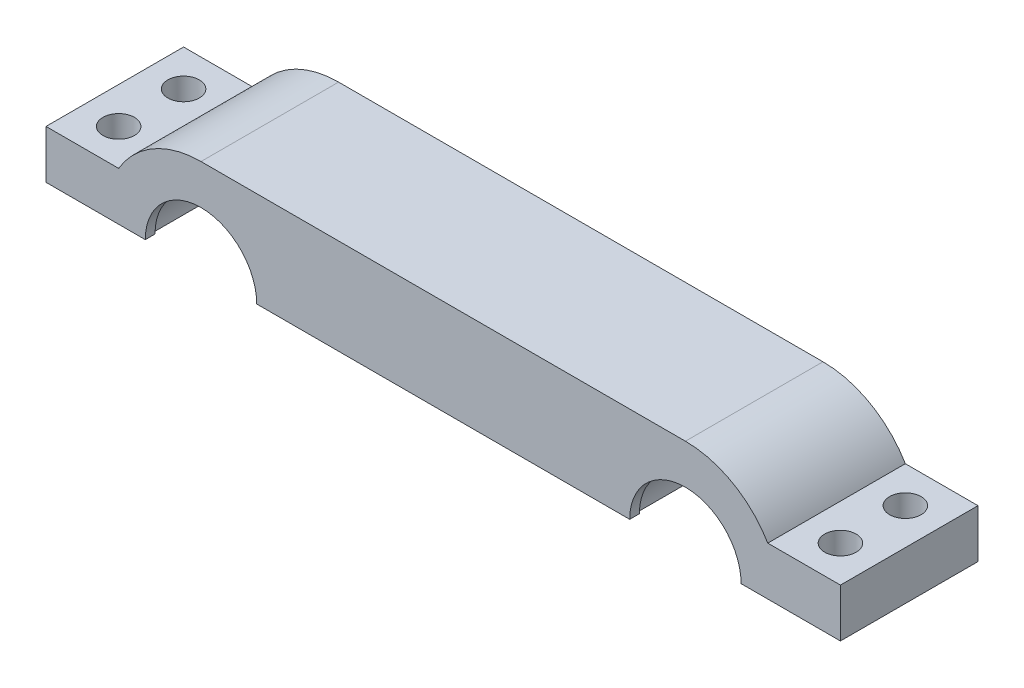
SolidWorks part; units mm, degrees
ref_plane "Front Plane" through (0, 0, 0) normal (0, 0, 1) x (1, 0, 0)
ref_plane "Top Plane" through (0, 0, 0) normal (0, 1, 0) x (1, 0, 0)
ref_plane "Right Plane" through (0, 0, 0) normal (1, 0, 0) x (0, 0, -1)
sketch "Sketch1" plane through (0, 0, 0) normal (0, 0, 1) x (1, 0, 0)
  line L1 (-41, 0) -> (41, 0)
  line L2 (-41, 0) -> (-41, 25)
  line L3 (-41, 25) -> (41, 25)
  line L4 (41, 0) -> (41, 25)
  point P5 (0, 0)
  dimension "D1" = 25
  dimension "D2" = 82
extrude "Boss-Extrude1" add sketch "Sketch1" along normal blind 14.2
sketch "Sketch2" plane through (0, 0, 0) normal (0, 0, -1) x (-1, 0, 0)
  line L0 (41, 0) -> (-41, 0) construction
  line L1 (-31, 0) -> (-19, 0)
  line L2 (19, 0) -> (31, 0)
  arc A0 (-31, 0) -> (-19, 0) centre (-25, 0) cw
  arc A1 (31, 0) -> (19, 0) centre (25, 0) ccw
  dimension "D1" = 6
  dimension "D3" = 6
  dimension "D2" = 10
  dimension "D4" = 10
extrude "Cut-Extrude3" cut sketch "Sketch2" against normal up to surface (14.2 mm away) up to face at (0, 12.5, 14.2)
sketch "Sketch4" plane through (0, 0, 0) normal (0, 0, -1) x (-1, 0, 0)
  line L0 (-30.75, 0) -> (-31, 0)
  line L1 (-19.25, 0) -> (-19, 0)
  line L2 (19, 0) -> (19.25, 0)
  line L3 (31, 0) -> (30.75, 0)
  line L4 (19, 0) -> (-19, 0) construction
  arc A0 (-31, 0) -> (-19, 0) centre (-25, 0) cw
  arc A1 (-30.75, 0) -> (-19.25, 0) centre (-25, 0) cw
  arc A2 (19, 0) -> (31, 0) centre (25, 0) cw
  arc A3 (19.25, 0) -> (30.75, 0) centre (25, 0) cw
  dimension "D1" = 5.75
extrude "Boss-Extrude2" add sketch "Sketch4" against normal blind 1
extrude "Boss-Extrude3" add sketch "Sketch4<2>" against normal blind 1 from offset 13.2 offset against normal yes
sketch "Sketch4<2>" plane through (0, 0, 0) normal (0, 0, -1) x (-1, 0, 0) same geometry as "Sketch4"
sketch "Sketch5" plane through (0, 0, 0) normal (0, 0, -1) x (-1, 0, 0)
  line L0 (19.25, 0) -> (-19.25, 0) construction
  line L1 (-6.5, 0) -> (6.5, 0)
  arc A0 (6.5, 0) -> (-6.5, 0) centre (0, 0) ccw
  dimension "D1" = 6.5
extrude "Cut-Extrude4" cut sketch "Sketch5" against normal blind 3.25 from offset 4.5 offset against normal yes
sketch "Sketch6" plane through (0, 0, 0) normal (0, 0, -1) x (-1, 0, 0)
  line L0 (19.25, 0) -> (-19.25, 0) construction
  line L1 (-2.625, 0) -> (2.625, 0)
  arc A0 (2.625, 0) -> (-2.625, 0) centre (0, 0) ccw
  dimension "D1" = 2.625
extrude "Cut-Extrude5" cut sketch "Sketch6" against normal up to surface (4.5 mm away) up to face at (0, 3.25, 4.5)
sketch "Sketch7" plane through (0, 0, 0) normal (0, 0, -1) x (-1, 0, 0)
  line L0 (-41, 5) -> (-33.5, 5)
  line L2 (-25, 9.8615) -> (25, 9.8615)
  line L3 (33.5, 5) -> (41, 5)
  line L5 (-30.75, 0) -> (-41, 0) construction
  line L6 (-41, 0) -> (-41, 25) construction
  line L7 (-41, 5) -> (-41, 25)
  line L8 (-41, 25) -> (41, 25)
  line L9 (41, 25) -> (41, 5)
  arc A0 (-33.5, 5) -> (-25, 9.8615) centre (-25, 0) cw
  arc A1 (25, 9.8615) -> (33.5, 5) centre (25, 0) cw
  arc A2 (-19.25, 0) -> (-30.75, 0) centre (-25, 0) ccw construction
  arc A3 (30.75, 0) -> (19.25, 0) centre (25, 0) ccw construction
  dimension "D2" = 7.5
  dimension "D1" = 5
extrude "Cut-Extrude6" cut sketch "Sketch7" against normal up to surface (14.2 mm away) up to face at (0, 7.6875, 14.2)
sketch "Sketch8" plane through (0, 5, 0) normal (0, 1, 0) x (1, 0, 0)
  line L0 (41, 0) -> (33.5, 0) construction
  line L1 (41, -14.2) -> (41, 0) construction
  line L2 (33.5, -14.2) -> (41, -14.2) construction
  line L3 (0, -7.81) -> (0, 7.81) construction
  circle A0 centre (37.25, -3.75) radius 1.625
  circle A1 centre (37.25, -10.45) radius 1.625
  circle A2 centre (-37.25, -3.75) radius 1.625
  circle A3 centre (-37.25, -10.45) radius 1.625
  dimension "D1" = 3.25
  dimension "D2" = 3.75
  dimension "D3" = 3.75
  dimension "D4" = 3.75
  dimension "D5" = 3.75
extrude "Cut-Extrude7" cut sketch "Sketch8" against normal up to surface (5 mm away) up to face at (33.375, 0, 7.1)
